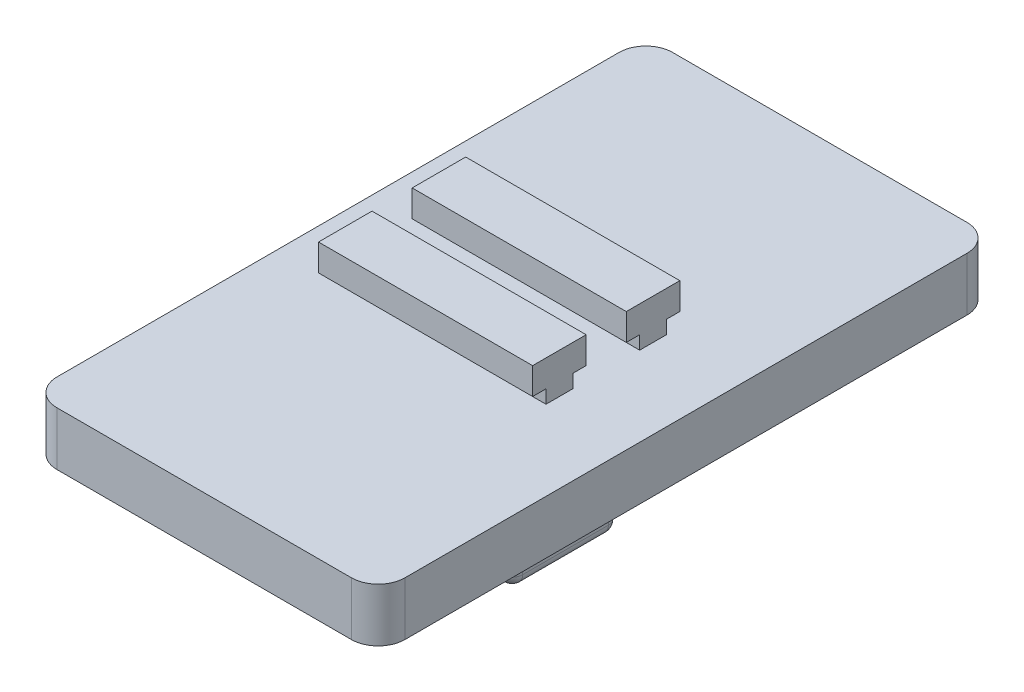
SolidWorks part; units mm, degrees
ref_plane "Front Plane" through (0, 0, 0) normal (0, 0, 1) x (1, 0, 0)
ref_plane "Top Plane" through (0, 0, 0) normal (0, 1, 0) x (1, 0, 0)
ref_plane "Right Plane" through (0, 0, 0) normal (1, 0, 0) x (0, 0, -1)
sketch "Sketch1" plane through (0, 0, 0) normal (1, 0, 0) x (0, 0, -1)
  line L1 (-57.5, 0) -> (57.5, 0)
  line L2 (-57.5, 0) -> (-57.5, 10)
  line L3 (-57.5, 10) -> (57.5, 10)
  line L4 (57.5, 0) -> (57.5, 10)
  point P4 (0, 0)
  dimension "D1" = 115
  dimension "D2" = 10
extrude "Boss-Extrude1" add sketch "Sketch1" along normal blind 65
sketch "Sketch2" plane through (65, 0, 0) normal (1, 0, 0) x (0, 0, -1)
  line L0 (-11.25, 10) -> (-11.25, 12.5)
  line L1 (-11.25, 12.5) -> (-13.75, 12.5)
  line L2 (-13.75, 12.5) -> (-13.75, 17.5)
  line L3 (-13.75, 17.5) -> (-3.75, 17.5)
  line L4 (-3.75, 17.5) -> (-3.75, 12.5)
  line L5 (-3.75, 12.5) -> (-6.25, 12.5)
  line L6 (-6.25, 12.5) -> (-6.25, 10)
  line L7 (-6.25, 10) -> (-11.25, 10)
  line L8 (57.5, 10) -> (-57.5, 10) construction
  dimension "D1" = 2.5
  dimension "D2" = 2.5
  dimension "D3" = 5
  dimension "D4" = 5
  dimension "D5" = 6.25
extrude "Boss-Extrude2" add sketch "Sketch2" against normal blind 40 from offset 14.9 offset against normal yes
mirror "Mirror1" of "Boss-Extrude2"
sketch "Sketch3" plane through (0, 0, 0) normal (0, -1, 0) x (1, 0, 0)
  line L0 (0, 0) -> (1000, 0) construction
  line L1 (50, 0) -> (-50, 0) construction
  line L2 (65, -57.5) -> (0, -57.5) construction
  circle A0 centre (32.5, 0) radius 20
  point P9 (32.5, -57.5)
  dimension "D1" = 40
extrude "Boss-Extrude3" add sketch "Sketch3" along normal blind 5
sketch "Sketch4" plane through (0, -5, 0) normal (0, -1, 0) x (1, 0, 0)
  line L0 (65, -57.5) -> (0, -57.5) construction
  line L1 (22.5, 10) -> (42.5, 10)
  line L2 (22.5, 10) -> (22.5, -10)
  line L3 (22.5, -10) -> (42.5, -10)
  line L4 (42.5, 10) -> (42.5, -10)
  point P4 (22.5, 0)
  point P8 (32.5, -57.5)
  point P9 (32.5, -10)
  dimension "D1" = 20
  dimension "D2" = 20
extrude "Boss-Extrude4" add sketch "Sketch4" along normal blind 20
fillet "Fillet1" radius 3 1 edges at (32.5, -5, -20)
fillet "Fillet2" radius 2 12 edges at (22.5, -5, 0) (32.5, -5, -10) (42.5, -5, 0) (32.5, -5, 10) (22.5, -15, 10) (32.5, -25, 10) (42.5, -25, 0) (22.5, -25, 0) (32.5, -25, -10) (22.5, -15, -10) (42.5, -15, -10) (42.5, -15, 10)
fillet "Fillet3" radius 5 4 edges at (0, 5, 57.5) (65, 5, 57.5) (0, 5, -57.5) (65, 5, -57.5)
sketch "Sketch10" plane through (0, 0, 10) normal (0, 0, 1) x (1, 0, 0)
  line L2 (42.5, -25) -> (22.5, -25) construction
  circle A0 centre (32.5, -10) radius 2.5
  point P2 (0, 0)
  point P3 (32.5, -25)
  dimension "D1" = 5
  dimension "D5" = 15
extrude "Cut-Extrude5" cut sketch "Sketch10" against normal up to surface (20 mm away) up to face at (32.5, -15, -10)
fillet "Fillet4" radius 2 2 edges at (35, -10, 10) (32.5, -12.5, -10)
